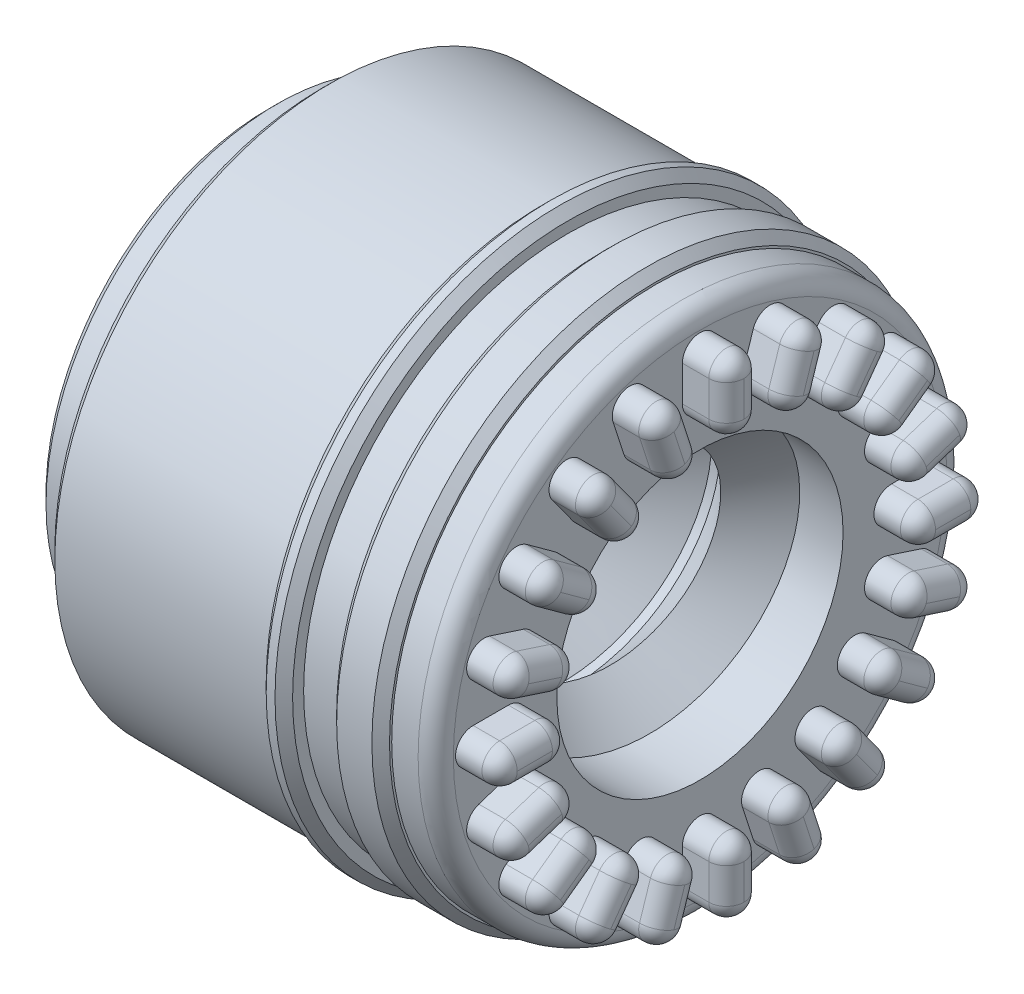
SolidWorks part; units mm, degrees
ref_plane "前视基准面" through (0, 0, 0) normal (0, 0, 1) x (1, 0, 0)
ref_plane "上视基准面" through (0, 0, 0) normal (0, 1, 0) x (1, 0, 0)
ref_plane "右视基准面" through (0, 0, 0) normal (1, 0, 0) x (0, 0, -1)
other "Configuration Table"
sketch "草图1" plane through (0, 0, 0) normal (0, 0, 1) x (1, 0, 0)
  line L0 (-19.681, 0) -> (18.3885, 0) construction
  line L1 (0, 0) -> (8.6, 0)
  line L2 (5.2, 6.25) -> (5.2, 6.45)
  line L3 (0, 0) -> (0, 2.6)
  line L4 (0, 2.6) -> (-1.2, 2.6)
  line L5 (-1.2, 2.6) -> (-1.2, 5.25)
  line L6 (-1.2, 5.25) -> (0, 5.25)
  line L7 (0, 5.25) -> (0, 6.25)
  line L8 (0, 6.25) -> (5.2, 6.25)
  line L9 (5.2, 6.45) -> (5.6, 6.45)
  line L10 (5.6, 6.45) -> (5.6, 6)
  line L11 (5.6, 6) -> (6.4, 6)
  line L12 (6.4, 6) -> (6.4, 6.25)
  line L13 (6.4, 6.25) -> (7.6, 6.25)
  line L14 (7.6, 6.25) -> (7.6, 6)
  line L15 (7.6, 6) -> (8.6, 6)
  line L16 (8.6, 6) -> (8.6, 0)
  point P4 (8.6582, 6.25)
  point P17 (15.1195, 0)
  dimension "D1" = 6.25
  dimension "D2" = 2.6
  dimension "D3" = 5.25
  dimension "D4" = 1.2
  dimension "D5" = 0.2
  dimension "D6" = 6
  dimension "D7" = 0.4
  dimension "D8" = 0.8
  dimension "D9" = 1.2
  dimension "D10" = 5.2
  dimension "D11" = 1
revolve "旋转1" add sketch "草图1" angle 360 about L0
sketch "草图3" plane through (8.6, 0, 0) normal (1, 0, 0) x (0, 0, -1)
  line L0 (0, 5.15) -> (0, 4.35) construction
  line L1 (0.4, 5.15) -> (0.4, 4.35)
  line L2 (-0.4, 5.15) -> (-0.4, 4.35)
  line L3 (1.5914, 4.8979) -> (1.3442, 4.1371) construction
  line L4 (1.9719, 4.7743) -> (1.7246, 4.0135)
  line L5 (1.211, 5.0215) -> (0.9638, 4.2607)
  line L6 (3.0271, 4.1664) -> (2.5569, 3.5192) construction
  line L7 (3.3507, 3.9313) -> (2.8805, 3.2841)
  line L8 (2.7035, 4.4016) -> (2.2333, 3.7543)
  line L9 (4.1664, 3.0271) -> (3.5192, 2.5569) construction
  line L10 (4.4016, 2.7035) -> (3.7543, 2.2333)
  line L11 (3.9313, 3.3507) -> (3.2841, 2.8805)
  line L12 (4.8979, 1.5914) -> (4.1371, 1.3442) construction
  line L13 (5.0215, 1.211) -> (4.2607, 0.9638)
  line L14 (4.7743, 1.9719) -> (4.0135, 1.7246)
  line L15 (5.15, 0) -> (4.35, 0) construction
  line L16 (5.15, -0.4) -> (4.35, -0.4)
  line L17 (5.15, 0.4) -> (4.35, 0.4)
  line L18 (4.8979, -1.5914) -> (4.1371, -1.3442) construction
  line L19 (4.7743, -1.9719) -> (4.0135, -1.7246)
  line L20 (5.0215, -1.211) -> (4.2607, -0.9638)
  line L21 (4.1664, -3.0271) -> (3.5192, -2.5569) construction
  line L22 (3.9313, -3.3507) -> (3.2841, -2.8805)
  line L23 (4.4016, -2.7035) -> (3.7543, -2.2333)
  line L24 (3.0271, -4.1664) -> (2.5569, -3.5192) construction
  line L25 (2.7035, -4.4016) -> (2.2333, -3.7543)
  line L26 (3.3507, -3.9313) -> (2.8805, -3.2841)
  line L27 (1.5914, -4.8979) -> (1.3442, -4.1371) construction
  line L28 (1.211, -5.0215) -> (0.9638, -4.2607)
  line L29 (1.9719, -4.7743) -> (1.7246, -4.0135)
  line L30 (0, -5.15) -> (0, -4.35) construction
  line L31 (-0.4, -5.15) -> (-0.4, -4.35)
  line L32 (0.4, -5.15) -> (0.4, -4.35)
  line L33 (-1.5914, -4.8979) -> (-1.3442, -4.1371) construction
  line L34 (-1.9719, -4.7743) -> (-1.7246, -4.0135)
  line L35 (-1.211, -5.0215) -> (-0.9638, -4.2607)
  line L36 (-3.0271, -4.1664) -> (-2.5569, -3.5192) construction
  line L37 (-3.3507, -3.9313) -> (-2.8805, -3.2841)
  line L38 (-2.7035, -4.4016) -> (-2.2333, -3.7543)
  line L39 (-4.1664, -3.0271) -> (-3.5192, -2.5569) construction
  line L40 (-4.4016, -2.7035) -> (-3.7543, -2.2333)
  line L41 (-3.9313, -3.3507) -> (-3.2841, -2.8805)
  line L42 (-4.8979, -1.5914) -> (-4.1371, -1.3442) construction
  line L43 (-5.0215, -1.211) -> (-4.2607, -0.9638)
  line L44 (-4.7743, -1.9719) -> (-4.0135, -1.7246)
  line L45 (-5.15, 0) -> (-4.35, 0) construction
  line L46 (-5.15, 0.4) -> (-4.35, 0.4)
  line L47 (-5.15, -0.4) -> (-4.35, -0.4)
  line L48 (-4.8979, 1.5914) -> (-4.1371, 1.3442) construction
  line L49 (-4.7743, 1.9719) -> (-4.0135, 1.7246)
  line L50 (-5.0215, 1.211) -> (-4.2607, 0.9638)
  line L51 (-4.1664, 3.0271) -> (-3.5192, 2.5569) construction
  line L52 (-3.9313, 3.3507) -> (-3.2841, 2.8805)
  line L53 (-4.4016, 2.7035) -> (-3.7543, 2.2333)
  line L54 (-3.0271, 4.1664) -> (-2.5569, 3.5192) construction
  line L55 (-2.7035, 4.4016) -> (-2.2333, 3.7543)
  line L56 (-3.3507, 3.9313) -> (-2.8805, 3.2841)
  line L57 (-1.5914, 4.8979) -> (-1.3442, 4.1371) construction
  line L58 (-1.211, 5.0215) -> (-0.9638, 4.2607)
  line L59 (-1.9719, 4.7743) -> (-1.7246, 4.0135)
  circle A0 centre (0, 0) radius 4.75 construction
  arc A1 (0.4, 5.15) -> (-0.4, 5.15) centre (0, 5.15) ccw
  arc A2 (-0.4, 4.35) -> (0.4, 4.35) centre (0, 4.35) ccw
  arc A3 (1.9719, 4.7743) -> (1.211, 5.0215) centre (1.5914, 4.8979) ccw
  arc A4 (0.9638, 4.2607) -> (1.7246, 4.0135) centre (1.3442, 4.1371) ccw
  arc A5 (3.3507, 3.9313) -> (2.7035, 4.4016) centre (3.0271, 4.1664) ccw
  arc A6 (2.2333, 3.7543) -> (2.8805, 3.2841) centre (2.5569, 3.5192) ccw
  arc A7 (4.4016, 2.7035) -> (3.9313, 3.3507) centre (4.1664, 3.0271) ccw
  arc A8 (3.2841, 2.8805) -> (3.7543, 2.2333) centre (3.5192, 2.5569) ccw
  arc A9 (5.0215, 1.211) -> (4.7743, 1.9719) centre (4.8979, 1.5914) ccw
  arc A10 (4.0135, 1.7246) -> (4.2607, 0.9638) centre (4.1371, 1.3442) ccw
  arc A11 (5.15, -0.4) -> (5.15, 0.4) centre (5.15, 0) ccw
  arc A12 (4.35, 0.4) -> (4.35, -0.4) centre (4.35, 0) ccw
  arc A13 (4.7743, -1.9719) -> (5.0215, -1.211) centre (4.8979, -1.5914) ccw
  arc A14 (4.2607, -0.9638) -> (4.0135, -1.7246) centre (4.1371, -1.3442) ccw
  arc A15 (3.9313, -3.3507) -> (4.4016, -2.7035) centre (4.1664, -3.0271) ccw
  arc A16 (3.7543, -2.2333) -> (3.2841, -2.8805) centre (3.5192, -2.5569) ccw
  arc A17 (2.7035, -4.4016) -> (3.3507, -3.9313) centre (3.0271, -4.1664) ccw
  arc A18 (2.8805, -3.2841) -> (2.2333, -3.7543) centre (2.5569, -3.5192) ccw
  arc A19 (1.211, -5.0215) -> (1.9719, -4.7743) centre (1.5914, -4.8979) ccw
  arc A20 (1.7246, -4.0135) -> (0.9638, -4.2607) centre (1.3442, -4.1371) ccw
  arc A21 (-0.4, -5.15) -> (0.4, -5.15) centre (0, -5.15) ccw
  arc A22 (0.4, -4.35) -> (-0.4, -4.35) centre (0, -4.35) ccw
  arc A23 (-1.9719, -4.7743) -> (-1.211, -5.0215) centre (-1.5914, -4.8979) ccw
  arc A24 (-0.9638, -4.2607) -> (-1.7246, -4.0135) centre (-1.3442, -4.1371) ccw
  arc A25 (-3.3507, -3.9313) -> (-2.7035, -4.4016) centre (-3.0271, -4.1664) ccw
  arc A26 (-2.2333, -3.7543) -> (-2.8805, -3.2841) centre (-2.5569, -3.5192) ccw
  arc A27 (-4.4016, -2.7035) -> (-3.9313, -3.3507) centre (-4.1664, -3.0271) ccw
  arc A28 (-3.2841, -2.8805) -> (-3.7543, -2.2333) centre (-3.5192, -2.5569) ccw
  arc A29 (-5.0215, -1.211) -> (-4.7743, -1.9719) centre (-4.8979, -1.5914) ccw
  arc A30 (-4.0135, -1.7246) -> (-4.2607, -0.9638) centre (-4.1371, -1.3442) ccw
  arc A31 (-5.15, 0.4) -> (-5.15, -0.4) centre (-5.15, 0) ccw
  arc A32 (-4.35, -0.4) -> (-4.35, 0.4) centre (-4.35, 0) ccw
  arc A33 (-4.7743, 1.9719) -> (-5.0215, 1.211) centre (-4.8979, 1.5914) ccw
  arc A34 (-4.2607, 0.9638) -> (-4.0135, 1.7246) centre (-4.1371, 1.3442) ccw
  arc A35 (-3.9313, 3.3507) -> (-4.4016, 2.7035) centre (-4.1664, 3.0271) ccw
  arc A36 (-3.7543, 2.2333) -> (-3.2841, 2.8805) centre (-3.5192, 2.5569) ccw
  arc A37 (-2.7035, 4.4016) -> (-3.3507, 3.9313) centre (-3.0271, 4.1664) ccw
  arc A38 (-2.8805, 3.2841) -> (-2.2333, 3.7543) centre (-2.5569, 3.5192) ccw
  arc A39 (-1.211, 5.0215) -> (-1.9719, 4.7743) centre (-1.5914, 4.8979) ccw
  arc A40 (-1.7246, 4.0135) -> (-0.9638, 4.2607) centre (-1.3442, 4.1371) ccw
  point P5 (0, 4.75)
  point P14 (1.4678, 4.5175)
  point P21 (2.792, 3.8428)
  point P28 (3.8428, 2.792)
  point P35 (4.5175, 1.4678)
  point P42 (4.75, 0)
  point P49 (4.5175, -1.4678)
  point P56 (3.8428, -2.792)
  point P63 (2.792, -3.8428)
  point P70 (1.4678, -4.5175)
  point P77 (0, -4.75)
  point P84 (-1.4678, -4.5175)
  point P91 (-2.792, -3.8428)
  point P98 (-3.8428, -2.792)
  point P105 (-4.5175, -1.4678)
  point P112 (-4.75, 0)
  point P119 (-4.5175, 1.4678)
  point P126 (-3.8428, 2.792)
  point P133 (-2.792, 3.8428)
  point P140 (-1.4678, 4.5175)
  point P145 (0, 0)
  dimension "D1" = 9.5
  dimension "D2" = 0.8
  dimension "D3" = 0.8
  dimension "D4" = 20
extrude "凸台-拉伸1" add sketch "草图3" along normal blind 1
fillet "圆角1" radius 0.4 80 edges at (9.6, 4.6411, 1.0874) (9.6, 3.7567, 1.2206) (9.6, 4.3939, 1.8483) (9.6, 5.2784, 1.715) (9.6, 4.0779, 2.4684) (9.6, 3.1956, 2.3218) (9.6, 3.6077, 3.1156) (9.6, 4.49, 3.2622) (9.6, 3.1156, 3.6077) (9.6, 2.3218, 3.1956) (9.6, 2.4684, 4.0779) (9.6, 3.2622, 4.49) (9.6, 1.8483, 4.3939) (9.6, 1.2206, 3.7567) (9.6, 1.0874, 4.6411) (9.6, 1.715, 5.2784) (9.6, 0.4, 4.75) (9.6, 0, 3.95) (9.6, -0.4, 4.75) (9.6, 0, 5.55) (9.6, -1.0874, 4.6411) (9.6, -1.2206, 3.7567) (9.6, -1.8483, 4.3939) (9.6, -1.715, 5.2784) (9.6, -2.4684, 4.0779) (9.6, -2.3218, 3.1956) (9.6, -3.1156, 3.6077) (9.6, -3.2622, 4.49) (9.6, -3.6077, 3.1156) (9.6, -3.1956, 2.3218) (9.6, -4.0779, 2.4684) (9.6, -4.49, 3.2622) (9.6, -4.3939, 1.8483) (9.6, -3.7567, 1.2206) (9.6, -4.6411, 1.0874) (9.6, -5.2784, 1.715) (9.6, -4.75, 0.4) (9.6, -3.95, 0) (9.6, -4.75, -0.4) (9.6, -5.55, 0) (9.6, -4.6411, -1.0874) (9.6, -3.7567, -1.2206) (9.6, -4.3939, -1.8483) (9.6, -5.2784, -1.715) (9.6, -4.0779, -2.4684) (9.6, -3.1956, -2.3218) (9.6, -3.6077, -3.1156) (9.6, -4.49, -3.2622) (9.6, -3.1156, -3.6077) (9.6, -2.3218, -3.1956) (9.6, -2.4684, -4.0779) (9.6, -3.2622, -4.49) (9.6, -1.8483, -4.3939) (9.6, -1.2206, -3.7567) (9.6, -1.0874, -4.6411) (9.6, -1.715, -5.2784) (9.6, -0.4, -4.75) (9.6, 0, -3.95) (9.6, 0.4, -4.75) (9.6, 0, -5.55) (9.6, 1.0874, -4.6411) (9.6, 1.2206, -3.7567) (9.6, 1.8483, -4.3939) (9.6, 1.715, -5.2784) (9.6, 2.4684, -4.0779) (9.6, 2.3218, -3.1956) (9.6, 3.1156, -3.6077) (9.6, 3.2622, -4.49) (9.6, 3.6077, -3.1156) (9.6, 3.1956, -2.3218) (9.6, 4.0779, -2.4684) (9.6, 4.49, -3.2622) (9.6, 4.3939, -1.8483) (9.6, 3.7567, -1.2206) (9.6, 4.6411, -1.0874) (9.6, 5.2784, -1.715) (9.6, 4.75, -0.4) (9.6, 3.95, 0) (9.6, 4.75, 0.4) (9.6, 5.55, 0)
sketch "草图4" plane through (8.6, 0, 0) normal (1, 0, 0) x (0, 0, -1)
  circle A0 centre (0, 0) radius 3.25
  dimension "D1" = 6.5
extrude "切除-拉伸1" cut sketch "草图4" against normal blind 6
fillet "圆角2" radius 0.4 1 edges at (8.6, 0, 6)
sketch "草图6" plane through (8.6, 0, 0) normal (1, 0, 0) x (0, 0, -1)
  circle A0 centre (0, 0) radius 3.25 construction
  circle A1 centre (0, 0) radius 3.25
curve "螺旋线/涡状线1" pitch 2 height 6 turns 3
sketch "草图7" plane through (0, 0, 0) normal (0, 1, 0) x (1, 0, 0)
  line L0 (8.6, -3.25) -> (6.8, -3.25)
  line L1 (8.6, -3.4271) -> (8.6, -2.7035) construction
  line L2 (6.8, -3.25) -> (7.7, -2.35)
  line L3 (7.7, -2.35) -> (8.6, -3.25)
  spline S0 degree 3 poles (8.6, -3.25) (8.5586, -3.25) (8.4749, -3.0808) (8.35, -2.3579) (8.225, -1.2761) (8.1, 0) (7.975, 1.2761) (7.85, 2.3579) (7.725, 3.0808) (7.6, 3.3346) (7.475, 3.0808) (7.35, 2.3579) (7.1833, 0.9155) (7.0167, -0.9155) (6.85, -2.3579) (6.725, -3.0808) (6.6, -3.3346) (6.475, -3.0808) (6.35, -2.3579) (6.1833, -0.9155) (6.0167, 0.9155) (5.85, 2.3579) (5.725, 3.0808) (5.6, 3.3346) (5.475, 3.0808) (5.35, 2.3579) (5.1833, 0.9155) (5.0167, -0.9155) (4.85, -2.3579) (4.725, -3.0808) (4.6, -3.3346) (4.475, -3.0808) (4.35, -2.3579) (4.1833, -0.9155) (4.0167, 0.9155) (3.85, 2.3579) (3.725, 3.0808) (3.6, 3.3346) (3.475, 3.0808) (3.35, 2.3579) (3.225, 1.2761) (3.1, 0) (2.975, -1.2761) (2.85, -2.3579) (2.7251, -3.0808) (2.6414, -3.25) (2.6, -3.25) knots 0 0 0 0 0.020833 0.041667 0.0625 0.083333 0.104167 0.125 0.145833 0.166667 0.1875 0.208333 0.229167 0.270833 0.291667 0.3125 0.333333 0.354167 0.375 0.395833 0.4375 0.458333 0.479167 0.5 0.520833 0.541667 0.5625 0.604167 0.625 0.645833 0.666667 0.6875 0.708333 0.729167 0.770833 0.791667 0.8125 0.833333 0.854167 0.875 0.895833 0.916667 0.9375 0.958333 0.979167 1 1 1 1 construction
  dimension "D1" = 1.8
sweep "扫描1" add profiles "草图7" path "螺旋线/涡状线1"
sketch "草图5" plane through (-1.2, 0, 0) normal (-1, 0, 0) x (0, 0, 1)
  line L0 (0, 8.3849) -> (0, -8.0884) construction
  line L1 (0, 0) -> (5.7994, -5.7994) construction
  line L2 (-3.424, 0) -> (3.0526, 0) construction
  circle A0 centre (0, 3.9) radius 0.8
  circle A1 centre (0, 0) radius 3.9 construction
  circle A2 centre (3.9, 0) radius 0.8
  circle A3 centre (0, -3.9) radius 0.8
  circle A4 centre (-3.9, 0) radius 0.8
  circle A5 centre (2.7577, -2.7577) radius 1
  point P19 (0, 0)
  dimension "D2" = 7.8
  dimension "D3" = 1.6
  dimension "D5" = 2
  dimension "D1" = 45
  dimension "D4" = 4
extrude "切除-拉伸2" cut sketch "草图5" against normal blind 3.6
chamfer "倒角1" distance 0.2 angle 45 7 edges at (5.6, 0, 6.45) (6.4, 0, 6.25) (7.6, 0, 6.25) (5.2, 0, 6.25) (-1.2, 0, 2.6) (-1.2, 0, 5.25) (0, 0, 6.25)
chamfer "倒角2" distance 0.8 angle 45 5 edges at (2.4, -2.7577, 3.7577) (2.4, -3.9, 0.8) (2.4, 0, 4.7) (2.4, 3.9, 0.8) (2.4, 0, -3.1)
